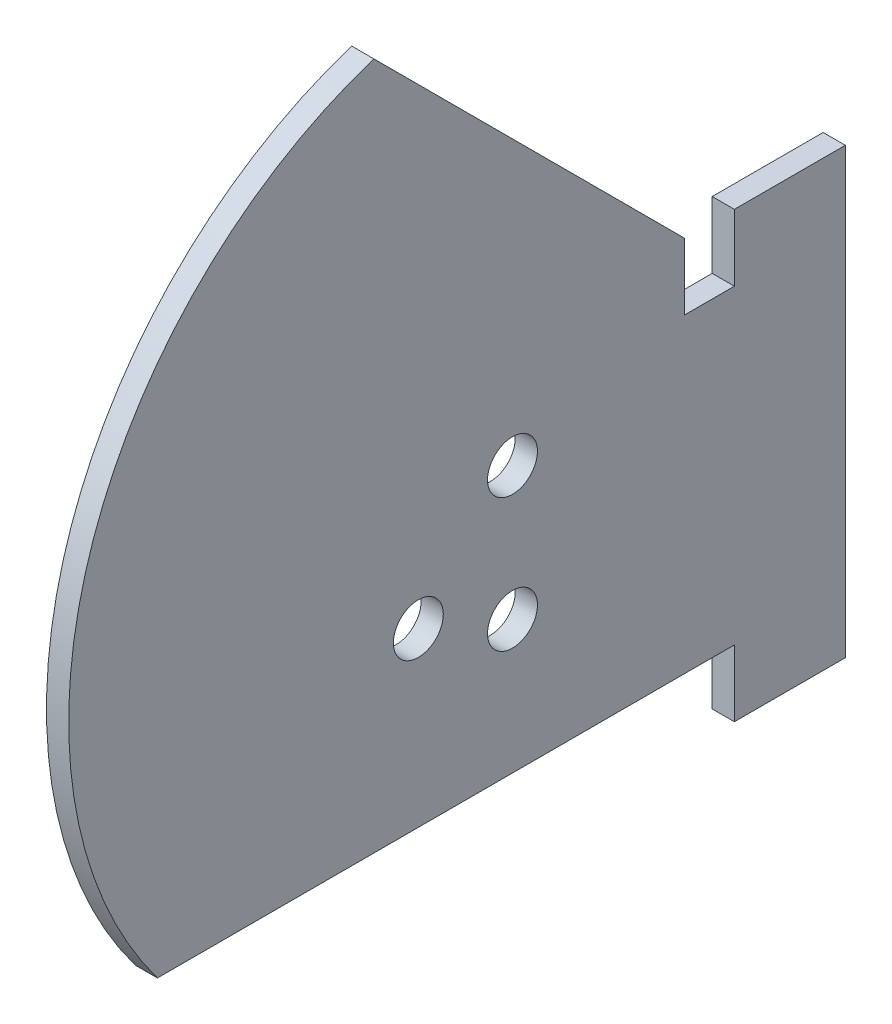
SolidWorks part; units mm, degrees
ref_plane "Front Plane" through (0, 0, 0) normal (0, 0, 1) x (1, 0, 0)
ref_plane "Top Plane" through (0, 0, 0) normal (0, 1, 0) x (1, 0, 0)
ref_plane "Right Plane" through (0, 0, 0) normal (1, 0, 0) x (0, 0, -1)
sketch "Sketch1" plane through (0, 0, 0) normal (1, 0, 0) x (0, 0, -1)
  line L0 (-16, 7) -> (15, 7) construction
  line L1 (-16, 14) -> (15, 14)
  line L2 (-16, 14) -> (-16, 0)
  line L3 (-16, 0) -> (15, 0)
  line L4 (15, 14) -> (15, 0)
  line L5 (0, 14) -> (0, 0) construction
  line L10 (0, 12) -> (-4.2426, 7.7574) construction
  line L11 (7.75, 14) -> (7.75, 17)
  line L12 (7.75, 17) -> (-6.2488, 30.9988)
  line L13 (15, 14) -> (10, 14)
  line L14 (15, 14) -> (15, 17)
  line L15 (15, 17) -> (10, 17)
  line L16 (10, 14) -> (10, 17)
  line L19 (15, 0) -> (10, 0)
  line L20 (15, 0) -> (15, -3)
  line L21 (15, -3) -> (10, -3)
  line L22 (10, 0) -> (10, -3)
  circle A2 centre (0, 12) radius 1.125
  circle A10 centre (0, 9) radius 3
  circle A11 centre (0, 6) radius 1.125
  circle A12 centre (-4.2426, 7.7574) radius 1.125
  circle A13 centre (-2.1213, 9.8787) radius 3
  circle A14 centre (0, 12) radius 20
  dimension "D1" = 2.25
  dimension "D2" = 5
  dimension "D7" = 6
  dimension "D3" = 14
  dimension "D4" = 15
  dimension "D5" = 16
  dimension "D6" = 45
  dimension "D8" = 2.25
  dimension "D9" = 3
  dimension "D10" = 5
extrude "Boss-Extrude1" add sketch "Sketch1" along normal blind 1 contours A14 L2 L1 | L4 L1 L2 L3 A13 A2 A10 A11 A12 | A13 A10 A11 A2 | A10 A13 A2 | A2 A13 A12 A10 | L16 L1 L14 L15 | L21 A14 L20 L3 L22 | A14 L21 L20 region at (0, 18.9184, 8.0379) region at (0, 13.6599, 4.125) region at (0, 15.5, -12.5) region at (0, -1.3973, -12.286) region at (0, -2.422, -14.422) region at (0, 10.6523, 3.3124) region at (0, 8.7048, -1.3893) region at (0, 9.2427, 1.1421)
